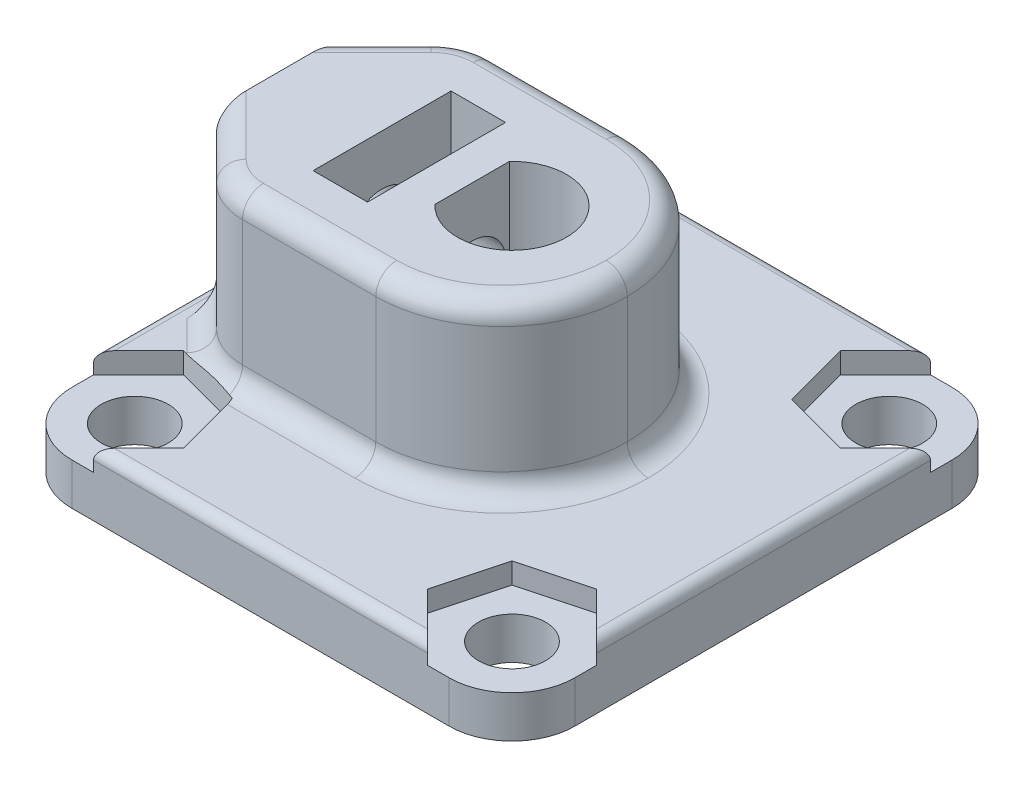
SolidWorks part; units mm, degrees
ref_plane "Front Plane" through (0, 0, 0) normal (0, 0, 1) x (1, 0, 0)
ref_plane "Top Plane" through (0, 0, 0) normal (0, 1, 0) x (1, 0, 0)
ref_plane "Right Plane" through (0, 0, 0) normal (1, 0, 0) x (0, 0, -1)
sketch "Sketch1" plane through (0, 0, 0) normal (0, 1, 0) x (1, 0, 0)
  line L1 (12, -12) -> (-12, -12)
  line L2 (12, -12) -> (12, 12)
  line L3 (12, 12) -> (-12, 12)
  line L4 (-12, -12) -> (-12, 12)
  line L5 (12, -12) -> (-12, 12) construction
  line L6 (12, 12) -> (-12, -12) construction
  point P0 (0, 0)
  dimension "D1" = 24
  dimension "D2" = 24
extrude "Boss-Extrude1" add sketch "Sketch1" along normal blind 3
sketch "Sketch2" plane through (0, 3, 0) normal (0, 1, 0) x (1, 0, 0)
  line L1 (-11.1, 6) -> (5.5, 6)
  line L2 (-11.1, 6) -> (-11.1, -6)
  line L3 (-11.1, -6) -> (5.5, -6)
  line L4 (5.5, 6) -> (5.5, -6)
  point P4 (5.5, 0)
  dimension "D1" = 5.5
  dimension "D2" = 11.1
  dimension "D3" = 12
extrude "Boss-Extrude2" add sketch "Sketch2" along normal blind 8
sketch "Sketch3" plane through (0, 11, 0) normal (0, 1, 0) x (1, 0, 0)
  line L0 (-1.9, 1.7748) -> (-1.9, -1.7748)
  arc A0 (-1.9, -1.7748) -> (-1.9, 1.7748) centre (0, 0) ccw
  dimension "D2" = 2.6
  dimension "D1" = 1.9
extrude "Cut-Extrude1" cut sketch "Sketch3" against normal through all contours A0 L0
sketch "Sketch4" plane through (-11.1, 0, 0) normal (-1, 0, 0) x (0, 0, 1)
  line L0 (6, 11) -> (6, 3) construction
  circle A0 centre (0, 7) radius 1.6
  point P7 (6, 7)
  dimension "D1" = 3.2
extrude "Cut-Extrude2" cut sketch "Sketch4" against normal up to next contours A0
ref_plane "Plane1" through (-4.9, 0, 0) normal (1, 0, 0) x (0, 0, -1)
sketch "Sketch5" plane through (-4.9, 0, 0) normal (1, 0, 0) x (0, 0, -1)
  line L0 (6, 11) -> (-6, 11) construction
  line L1 (1.6454, 4.15) -> (3.2909, 7)
  line L2 (3.2909, 7) -> (1.6454, 9.85) construction
  line L3 (1.6454, 9.85) -> (-1.6454, 9.85) construction
  line L4 (-1.6454, 9.85) -> (-3.2909, 7) construction
  line L5 (-3.2909, 7) -> (-1.6454, 4.15)
  line L6 (-1.6454, 4.15) -> (1.6454, 4.15)
  line L7 (3.2909, 7) -> (3.2909, 11)
  line L8 (3.2909, 11) -> (-3.2909, 11)
  line L9 (-3.2909, 11) -> (-3.2909, 7)
  circle A0 centre (0, 7) radius 2.85 construction
  dimension "D1" = 5.7
extrude "Cut-Extrude3" cut sketch "Sketch5" against normal mid plane 2.6
fillet "Fillet3" radius 6 2 edges at (5.5, 7, 6) (5.5, 7, -6)
chamfer "Chamfer3" distance 3 angle 45 2 edges at (-11.1, 7, -6) (-11.1, 7, 6)
fillet "Fillet4" radius 3 2 edges at (-8.1, 7, 6) (-8.1, 7, -6)
fillet "Fillet6" radius 1 16 edges at (-10.0393, 11, 4.0607) (-8.0054, 11, 5.7716) (-3.6787, 11, 6) (3.7426, 11, 4.2426) (3.7426, 11, -4.2426) (-3.6787, 11, -6) (-8.0054, 11, -5.7716) (-10.0393, 3, 4.0607) (-8.0054, 3, 5.7716) (-3.6787, 3, 6) (3.7426, 3, 4.2426) (3.7426, 3, -4.2426) (-3.6787, 3, -6) (-8.0054, 3, -5.7716) (-10.0393, 11, -4.0607) (-10.0393, 3, -4.0607)
sketch "Sketch9" plane through (0, 3, 0) normal (0, 1, 0) x (1, 0, 0)
  line L1 (9, 9) -> (-9, 9) construction
  line L2 (9, 9) -> (9, -9) construction
  line L3 (9, -9) -> (-9, -9) construction
  line L4 (-9, 9) -> (-9, -9) construction
  circle A0 centre (-9, 9) radius 1.6
  circle A1 centre (9, 9) radius 1.6
  circle A2 centre (9, -9) radius 1.6
  circle A3 centre (-9, -9) radius 1.6
  point P4 (0, 9)
  point P6 (9, 0)
  dimension "D3" = 3.2
  dimension "D1" = 18
  dimension "D2" = 18
extrude "Cut-Extrude5" cut sketch "Sketch9" against normal through all
fillet "Fillet8" radius 3 4 edges at (12, 1.5, 12) (12, 1.5, -12) (-12, 1.5, -12) (-12, 1.5, 12)
fillet "Fillet9" radius 0.5 8 edges at (11.1213, 3, -11.1213) (12, 3, 0) (11.1213, 3, 11.1213) (0, 3, 12) (-11.1213, 3, 11.1213) (-12, 3, 0) (-11.1213, 3, -11.1213) (0, 3, -12)
sketch "Sketch10" plane through (0, 3, 0) normal (0, 1, 0) x (1, 0, 0)
  line L0 (0, 0) -> (9, -9) construction
  line L1 (5.8212, -9.8517) -> (8.1483, -12.1788)
  line L2 (8.1483, -12.1788) -> (11.327, -11.327) construction
  line L3 (11.327, -11.327) -> (12.1788, -8.1483) construction
  line L4 (12.1788, -8.1483) -> (9.8517, -5.8212)
  line L5 (9.8517, -5.8212) -> (6.673, -6.673)
  line L6 (6.673, -6.673) -> (5.8212, -9.8517)
  line L7 (12.1788, -8.1483) -> (13.1366, -9.1061)
  line L8 (13.1366, -9.1061) -> (9.1061, -13.1366)
  line L9 (9.1061, -13.1366) -> (8.1483, -12.1788)
  circle A0 centre (9, -9) radius 2.85 construction
  arc A1 (9, -12) -> (12, -9) centre (9, -9) ccw construction
  dimension "D1" = 5.7
extrude "Cut-Extrude6" cut sketch "Sketch10" against normal blind 1 and the other way through all
mirror "Mirror1" about plane through (0, 0, 0) normal (0, 0, 1) of "Cut-Extrude6"
mirror "Mirror2" about plane through (0, 0, 0) normal (1, 0, 0) of "Cut-Extrude6", "Mirror1"
